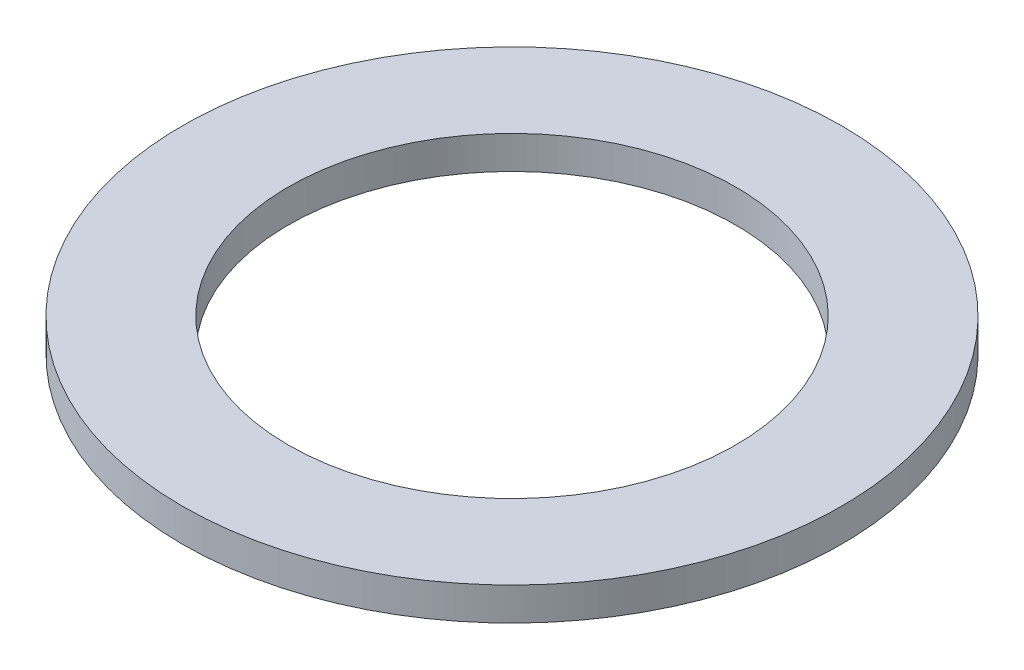
SolidWorks part; units mm, degrees
ref_plane "Front Plane" through (0, 0, 0) normal (0, 0, 1) x (1, 0, 0)
ref_plane "Top Plane" through (0, 0, 0) normal (0, 1, 0) x (1, 0, 0)
ref_plane "Right Plane" through (0, 0, 0) normal (1, 0, 0) x (0, 0, -1)
sketch "Sketch1" plane through (0, 0, 0) normal (0, 1, 0) x (1, 0, 0)
  circle A0 centre (0, 0) radius 70
  dimension "FLANGE_OD" = 140
extrude "Boss-Extrude1" add sketch "Sketch1" along normal blind 7
sketch "Sketch2" plane through (0, 0, 0) normal (0, 1, 0) x (1, 0, 0)
  circle A0 centre (0, 0) radius 47.5
  dimension "BORE_D" = 95
extrude "Cut-Extrude1" cut sketch "Sketch2" along normal through all
sketch "Sketch3" plane through (0, 7, 0) normal (0, 1, 0) x (1, 0, 0)
  circle A0 centre (0, 0) radius 27.6366 construction
  circle A1 centre (-27.6366, 0) radius 3.9457
  dimension "BOLT_D" = 7.8914
  dimension "BOLT_PCD" = 55.2731
extrude "Cut-Extrude2" cut sketch "Sketch3" against normal blind 5.4069 rebuild error yes
pattern_circular "CirPattern1" count 6 over 360 rebuild error yes
